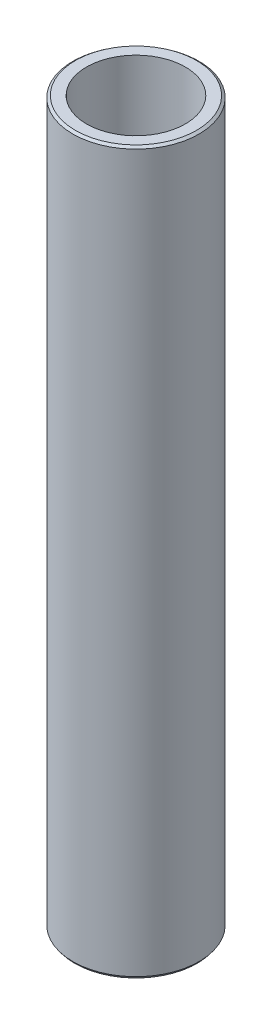
SolidWorks part; units mm, degrees
ref_plane "Front Plane" through (0, 0, 0) normal (0, 0, 1) x (1, 0, 0)
ref_plane "Top Plane" through (0, 0, 0) normal (0, 1, 0) x (1, 0, 0)
ref_plane "Right Plane" through (0, 0, 0) normal (1, 0, 0) x (0, 0, -1)
sketch "Sketch1" plane through (0, 0, 0) normal (0, 1, 0) x (1, 0, 0)
  circle A0 centre (0, 0) radius 52.5
  dimension "SHAFT_OD" = 105
extrude "Boss-Extrude1" add sketch "Sketch1" along normal blind 600
sketch "Sketch2" plane through (0, 0, 0) normal (0, 1, 0) x (1, 0, 0)
  circle A0 centre (0, 0) radius 41.1119
  dimension "BORE_D" = 82.2239
extrude "Cut-Extrude1" cut sketch "Sketch2" along normal through all
chamfer "Chamfer1" distance 1.585 angle 52.914 2 edges at (0, 600, 52.5) (0, 0, 52.5) first distance on face at (0, 600, 52.5) first distance on face at (0, 0, 41.1119)
